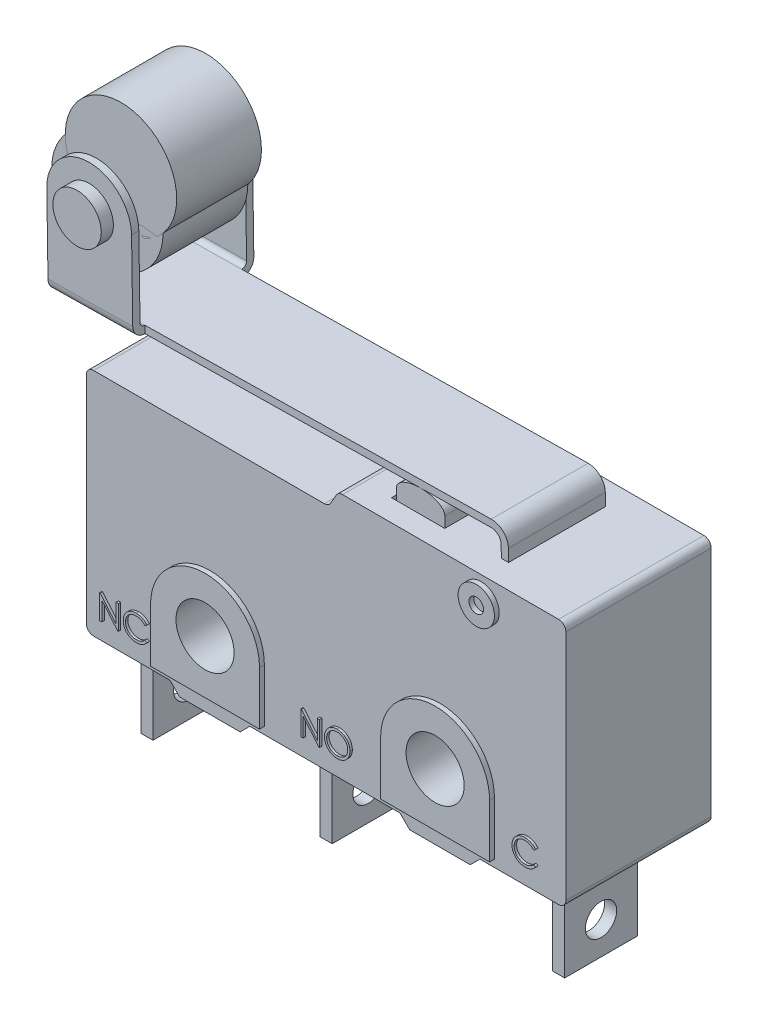
SolidWorks part; units mm, degrees
ref_plane "Plan de face" through (0, 0, 0) normal (0, 0, 1) x (1, 0, 0)
ref_plane "Plan de dessus" through (0, 0, 0) normal (0, 1, 0) x (1, 0, 0)
ref_plane "Plan de droite" through (0, 0, 0) normal (1, 0, 0) x (0, 0, -1)
sketch "Esquisse1" plane through (0, 0, 0) normal (0, 0, 1) x (1, 0, 0)
  line L0 (-7, 0) -> (-9.5, 0)
  line L1 (-9.5, 0) -> (-9.9, 0.4)
  line L2 (-9.9, 0.4) -> (-13.05, 0.4)
  line L3 (-13.35, 0.7) -> (-13.35, 9.6)
  line L4 (-13.05, 9.9) -> (-3.5232, 9.9)
  line L5 (-3.2634, 10.05) -> (-3.0325, 10.45)
  line L6 (-2.7726, 10.6) -> (6.15, 10.6)
  line L7 (6.45, 10.3) -> (6.45, 0.7)
  line L8 (6.15, 0.4) -> (2.9, 0.4)
  line L9 (2.9, 0.4) -> (2.5, 0)
  line L10 (2.5, 0) -> (0, 0)
  line L11 (0, 0) -> (-0.4, 0.4)
  line L12 (-0.4, 0.4) -> (-6.6, 0.4)
  line L13 (-6.6, 0.4) -> (-7, 0)
  line L14 (-8.25, 2.9) -> (-8.25, 0) construction
  line L15 (1.25, 2.9) -> (1.25, 0) construction
  circle A0 centre (-8.25, 2.9) radius 1.2
  circle A1 centre (1.25, 2.9) radius 1.2
  arc A2 (-3.5232, 9.9) -> (-3.2634, 10.05) centre (-3.5232, 10.2) ccw
  arc A3 (-3.0325, 10.45) -> (-2.7726, 10.6) centre (-2.7726, 10.3) cw
  arc A4 (-13.05, 0.4) -> (-13.35, 0.7) centre (-13.05, 0.7) cw
  arc A5 (-13.35, 9.6) -> (-13.05, 9.9) centre (-13.05, 9.6) cw
  arc A6 (6.45, 0.7) -> (6.15, 0.4) centre (6.15, 0.7) cw
  arc A7 (6.15, 10.6) -> (6.45, 10.3) centre (6.15, 10.3) cw
  point P23 (-3.35, 9.9)
  point P30 (-13.35, 9.9)
  dimension "D2" = 9.5
  dimension "D3" = 2.4
  dimension "D4" = 2.9
  dimension "D11" = 0.3
  dimension "D1" = 2.5
  dimension "D5" = 5.1
  dimension "D6" = 19.8
  dimension "D7" = 10
  dimension "D8" = 0.7
  dimension "D9" = 10.6
  dimension "D10" = 0.4
  dimension "D12" = 120
  dimension "D13" = 135
extrude "Boss.-Extru.1" add sketch "Esquisse1" along normal mid plane 6
sketch "Esquisse2" plane through (0, 0, 0) normal (0, 0, 1) x (1, 0, 0)
  line L0 (-10.5, 0.7) -> (-6, 0.7)
  line L1 (-6, 0.7) -> (-6, 2.9)
  line L2 (-10.5, 2.9) -> (-10.5, 0.7)
  line L3 (-1, 2.9) -> (-1, 0.7)
  line L4 (-1, 0.7) -> (3.5, 0.7)
  line L5 (3.5, 0.7) -> (3.5, 2.9)
  line L6 (6.45, 0.7) -> (6.45, 10.3) construction
  line L7 (6.15, 10.6) -> (-2.7726, 10.6) construction
  arc A0 (-6, 2.9) -> (-10.5, 2.9) centre (-8.25, 2.9) ccw
  circle A1 centre (-8.25, 2.9) radius 1.2 construction
  circle A2 centre (-8.25, 2.9) radius 1.2
  arc A3 (3.5, 2.9) -> (-1, 2.9) centre (1.25, 2.9) ccw
  circle A4 centre (1.25, 2.9) radius 1.2
  circle A5 centre (2.95, 9.6) radius 0.75
  circle A6 centre (2.95, 9.6) radius 0.3
  dimension "D1" = 2.25
  dimension "D5" = 3.5
  dimension "D7" = 1.5
  dimension "D8" = 0.6
  dimension "D2" = 2.2
  dimension "D4" = 5
  dimension "D6" = 1
  dimension "D3" = 2
extrude "Boss.-Extru.2" add sketch "Esquisse2" along normal mid plane 6.4
sketch "Esquisse3" plane through (0, 0, -3) normal (0, 0, -1) x (-1, 0, 0)
  text T0 "5A 125-250V~ 10T85" font "Century Gothic" height 1
extrude "Boss.-Extru.3" add sketch "Esquisse3" along normal blind 0.1
sketch "Esquisse18" plane through (0, 0, 0) normal (0, 0, 1) x (1, 0, 0)
  line L0 (6.15, 10.6) -> (-2.7726, 10.6) construction
  line L1 (-1.65, 10.6) -> (0.55, 10.6)
  line L2 (-1.65, 10.6) -> (-1.65, 8.6)
  line L3 (-1.65, 8.6) -> (0.55, 8.6)
  line L4 (0.55, 10.6) -> (0.55, 8.6)
  line L5 (6.45, 0.7) -> (6.45, 10.3) construction
  dimension "D1" = 5.9
  dimension "D2" = 2
  dimension "D3" = 2.2
extrude "Enlèv. mat.-Extru.3" cut sketch "Esquisse18" against normal mid plane 4.2
sketch "Esquisse9" plane through (0, 0, 0) normal (0, 0, 1) x (1, 0, 0)
  line L0 (2.785, 10.6) -> (2.7775, 11.0976)
  line L1 (6.15, 10.6) -> (-2.7726, 10.6) construction
  line L2 (2.3715, 11.4915) -> (-15.4265, 11.2241)
  line L3 (-15.4265, 11.2241) -> (-15.431, 11.5241)
  line L4 (-9.5, 0) -> (-7, 0) construction
  line L5 (-15.431, 11.5241) -> (2.367, 11.7915)
  line L6 (3.0775, 11.1021) -> (3.085, 10.6)
  line L7 (3.085, 10.6) -> (2.785, 10.6)
  line L8 (2.95, 9.6) -> (2.935, 10.6) construction
  arc A1 (2.7775, 11.0976) -> (2.3715, 11.4915) centre (2.3775, 11.0916) ccw
  arc A2 (2.367, 11.7915) -> (3.0775, 11.1021) centre (2.3775, 11.0916) cw
  circle A3 centre (-13.733, 15) radius 2.3 construction
  dimension "D4" = 0.4
  dimension "D5" = 0.7
  dimension "D9" = 4.6
  dimension "D1" = 0.3
  dimension "D2" = 0.3
  dimension "D3" = 2.2
  dimension "D6" = 18.5
  dimension "D7" = 1.75
  dimension "D10" = 3.75
  dimension "D11" = 15
extrude "Boss.-Extru.15" add sketch "Esquisse9" along normal mid plane 4
sketch "Esquisse10" plane through (0, 0, 0) normal (0, 0, 1) x (1, 0, 0)
  line L0 (-15.4265, 11.2241) -> (-15.4828, 14.9737)
  line L1 (-11.9832, 15.0263) -> (-11.9269, 11.2767)
  line L2 (-15.4265, 11.2241) -> (2.3715, 11.4915) construction
  line L3 (-11.9269, 11.2767) -> (-15.4265, 11.2241)
  arc A0 (-15.4828, 14.9737) -> (-11.9832, 15.0263) centre (-13.733, 15) cw
extrude "Boss.-Extru.16" add sketch "Esquisse10" along normal mid plane 5
sketch "Esquisse5" plane through (0, 0, 0) normal (0, 0, 1) x (1, 0, 0)
  line L0 (-1.55, 10.9474) -> (-1.55, 9.4474)
  line L2 (-1.55, 9.4474) -> (0.45, 9.4474)
  line L3 (0.45, 9.4474) -> (0.45, 10.9474)
  line L5 (-1.55, 10.9474) -> (0.45, 10.9474) construction
  line L6 (6.45, 0.7) -> (6.45, 10.3) construction
  line L7 (-11.9269, 11.2767) -> (2.3715, 11.4915) construction
  ellipse E0 centre (-0.55, 10.9474) end of major axis (0.45, 10.9474) minor radius 0.5 (0.45, 10.9474) -> (-1.55, 10.9474) ccw
  dimension "D1" = 0.5
  dimension "D2" = 2
  dimension "D4" = 2
  dimension "D5" = 6
extrude "Boss.-Extru.4" add sketch "Esquisse5" along normal mid plane 4 separate body
sketch "Esquisse11" plane through (0, 0, 0) normal (0, 0, 1) x (1, 0, 0)
  line L0 (-11.9314, 11.5767) -> (-15.431, 11.5241)
  line L2 (-15.431, 11.5241) -> (-15.5211, 17.5241)
  line L3 (-15.5211, 17.5241) -> (-12.0215, 17.5767)
  line L4 (-12.0215, 17.5767) -> (-11.9314, 11.5767)
  dimension "D1" = 6
extrude "Enlèv. mat.-Extru.1" cut sketch "Esquisse11" against normal mid plane 4.4
sketch "Esquisse12" plane through (0, 0, 0) normal (0, 0, 1) x (1, 0, 0)
  circle A0 centre (-13.733, 15) radius 1
  dimension "D1" = 2
extrude "Boss.-Extru.17" add sketch "Esquisse12" along normal mid plane 6
sketch "Esquisse13" plane through (0, 0, 0) normal (0, 0, 1) x (1, 0, 0)
  circle A0 centre (-13.733, 15) radius 2.3
  circle A1 centre (-13.733, 15) radius 2.3 construction
extrude "Boss.-Extru.18" add sketch "Esquisse13" along normal mid plane 3.5
fillet "Congé1" radius 0.2 2 edges at (-13.6812, 11.5504, 2.2) (-13.6812, 11.5504, -2.2)
fillet "Congé2" radius 0.5 2 edges at (-13.6767, 11.2504, 2.5) (-13.6767, 11.2504, -2.5)
sketch "Esquisse15" plane through (0, 0, 0) normal (0, 0, 1) x (1, 0, 0)
  line L1 (4.4, 0.5) -> (4.9, 0.5)
  line L2 (4.4, 0.5) -> (4.4, -3.6)
  line L3 (4.4, -3.6) -> (4.9, -3.6)
  line L4 (4.9, 0.5) -> (4.9, -3.6)
  line L5 (-6.6, 0.4) -> (-0.4, 0.4) construction
  line L6 (-5.2, 0.4) -> (-4.7, 0.4)
  line L7 (-5.2, 0.4) -> (-5.2, -3.6)
  line L8 (-5.2, -3.6) -> (-4.7, -3.6)
  line L9 (-4.7, 0.4) -> (-4.7, -3.6)
  line L10 (-13.05, 0.4) -> (-9.9, 0.4) construction
  line L11 (-12.6, 0.4) -> (-12.1, 0.4)
  line L12 (-12.6, 0.4) -> (-12.6, -3.6)
  line L13 (-12.6, -3.6) -> (-12.1, -3.6)
  line L14 (-12.1, 0.4) -> (-12.1, -3.6)
  line L16 (6.45, 0.7) -> (6.45, 10.3) construction
  dimension "D1" = 9.6
  dimension "D2" = 7.4
  dimension "D3" = 0.5
  dimension "D4" = 1.55
  dimension "D5" = 4
extrude "Boss.-Extru.19" add sketch "Esquisse15" along normal mid plane 3 separate body
sketch "Esquisse16" plane through (-12.6, 0, 0) normal (-1, 0, 0) x (0, 0, 1)
  circle A0 centre (0, -2.2572) radius 0.647
extrude "Enlèv. mat.-Extru.2" cut sketch "Esquisse16" against normal through all
sketch "Esquisse7" plane through (0, 0, -3) normal (0, 0, -1) x (-1, 0, 0)
  text T0 "1                 3                  2" font "Century Gothic" height 1
extrude "Boss.-Extru.5" add sketch "Esquisse7" along normal blind 0.1
sketch "Esquisse8" plane through (0, 0, 3) normal (0, 0, 1) x (1, 0, 0)
  text T0 "NC                NO                 C" font "Century Gothic" height 1
extrude "Boss.-Extru.6" add sketch "Esquisse8" along normal blind 0.1
sketch "Esquisse17" plane through (0, 0, 0) normal (0, 0, 1) x (1, 0, 0)
  line L1 (-9.5, 0) -> (-7, 0) construction
  arc A0 (-13.733, 15) -> (-13.1706, 16.5) centre (2.95, 9.6) cw construction
  circle A1 centre (-13.1706, 16.5) radius 2.3
  circle A2 centre (-13.733, 15) radius 2.3 construction
  dimension "D1" = 16.5
extrude "Boss.-Extru.20" add sketch "Esquisse17" along normal mid plane 3.5 separate body
